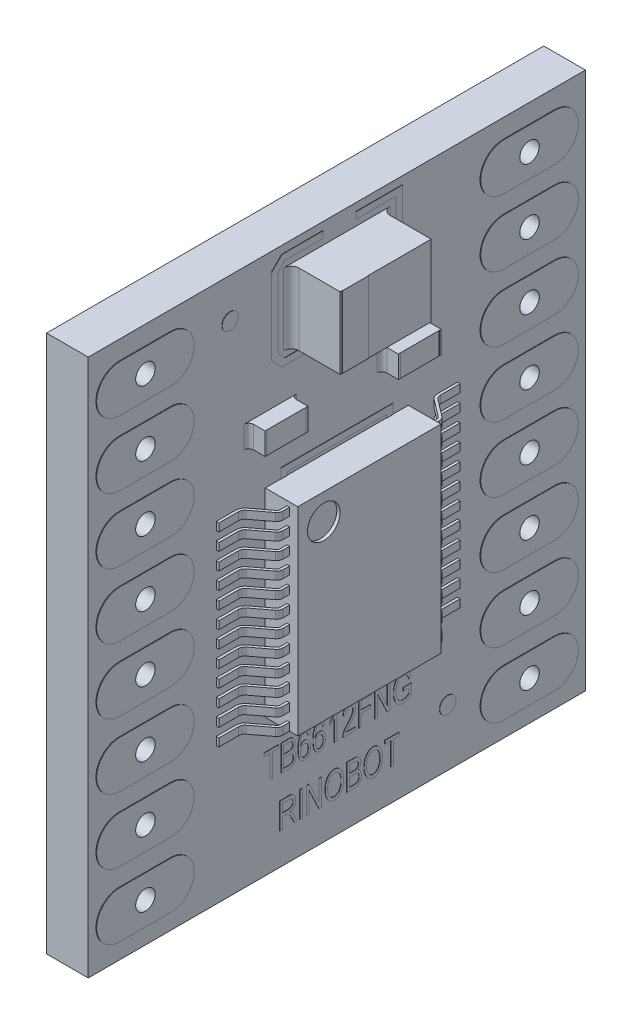
SolidWorks part; units mm, degrees
ref_plane "Front Plane" through (0, 0, 0) normal (0, 0, 1) x (1, 0, 0)
ref_plane "Top Plane" through (0, 0, 0) normal (0, 1, 0) x (1, 0, 0)
ref_plane "Right Plane" through (0, 0, 0) normal (1, 0, 0) x (0, 0, -1)
sketch "Sketch1" plane through (0, 0, 0) normal (1, 0, 0) x (0, 0, -1)
  line L1 (-10.4521, 10.4902) -> (10.4521, 10.4902)
  line L2 (-10.4521, 10.4902) -> (-10.4521, -10.4902)
  line L3 (-10.4521, -10.4902) -> (10.4521, -10.4902)
  line L4 (10.4521, 10.4902) -> (10.4521, -10.4902)
  line L5 (-10.4521, 10.4902) -> (10.4521, -10.4902) construction
  line L6 (-10.4521, -10.4902) -> (10.4521, 10.4902) construction
  point P0 (0, 0)
  dimension "D1" = 20.9804
  dimension "D2" = 20.9042
extrude "base extrudada" add sketch "Sketch1" along normal blind 1.6256
sketch "Sketch2" plane through (1.6256, 0, 0) normal (1, 0, 0) x (0, 0, -1)
  line L0 (-10.4521, -10.4902) -> (10.4521, -10.4902) construction
  line L1 (-2.794, 2.6162) -> (2.794, 2.6162)
  line L2 (-2.794, 2.6162) -> (-2.794, -5.1308)
  line L3 (-2.794, -5.1308) -> (2.794, -5.1308)
  line L4 (2.794, 2.6162) -> (2.794, -5.1308)
  line L5 (-2.794, 2.6162) -> (2.794, -5.1308) construction
  line L6 (-2.794, -5.1308) -> (2.794, 2.6162) construction
  point P0 (0, 0)
  dimension "D1" = 5.588
  dimension "D2" = 7.747
  dimension "D3" = 5.3594
extrude "Ci extrudado" add sketch "Sketch2" along normal blind 1.27
sketch "Sketch7" plane through (2.8956, 0, 0) normal (1, 0, 0) x (0, 0, -1)
  line L0 (-2.794, 2.6162) -> (-2.794, -5.1308) construction
  line L1 (2.794, 2.6162) -> (-2.794, 2.6162) construction
  circle A0 centre (-1.778, 1.6002) radius 0.635
  dimension "D1" = 1.27
  dimension "D2" = 1.016
  dimension "D3" = 1.016
extrude "furo dos Ci's" cut sketch "Sketch7" against normal blind 0.127
sketch "Sketch4" plane through (1.6256, 0, 0) normal (1, 0, 0) x (0, 0, -1)
  line L0 (-7.493, 8.8392) -> (0, 8.8392) construction
  line L1 (0, 8.8392) -> (7.493, 8.8392) construction
  line L2 (0, 0) -> (0, 8.8392) construction
  line L3 (10.4521, 10.4902) -> (-10.4521, 10.4902) construction
  circle A0 centre (-7.493, 8.8392) radius 0.381
  circle A1 centre (7.493, 8.8392) radius 0.381
  dimension "D2" = 0.762
  dimension "D1" = 14.986
  dimension "D3" = 1.27
extrude "furo dos pinos" cut sketch "Sketch4" against normal through all
sketch "Sketch5" plane through (1.6256, 0, 0) normal (1, 0, 0) x (0, 0, -1)
  line L0 (-8.4836, 8.8392) -> (-6.5024, 8.8392) construction
  line L1 (-8.4836, 9.7536) -> (-6.5024, 9.7536)
  line L2 (-8.4836, 7.9248) -> (-6.5024, 7.9248)
  line L3 (6.5024, 8.8392) -> (8.4836, 8.8392) construction
  line L4 (6.5024, 9.7536) -> (8.4836, 9.7536)
  line L5 (6.5024, 7.9248) -> (8.4836, 7.9248)
  arc A0 (-8.4836, 9.7536) -> (-8.4836, 7.9248) centre (-8.4836, 8.8392) ccw
  arc A1 (-6.5024, 7.9248) -> (-6.5024, 9.7536) centre (-6.5024, 8.8392) ccw
  arc A2 (6.5024, 9.7536) -> (6.5024, 7.9248) centre (6.5024, 8.8392) ccw
  arc A3 (8.4836, 7.9248) -> (8.4836, 9.7536) centre (8.4836, 8.8392) ccw
  circle A6 centre (7.493, 8.8392) radius 0.381 construction
  circle A7 centre (-7.493, 8.8392) radius 0.381 construction
  circle A8 centre (7.493, 8.8392) radius 0.381
  circle A9 centre (-7.493, 8.8392) radius 0.381
  point P3 (-7.493, 8.8392)
  point P8 (7.493, 8.8392)
  point P18 (7.493, 8.8392)
  dimension "D2" = 3.81
  dimension "D1" = 1.8288
extrude "base pra solda" add sketch "Sketch5" along normal blind 0.0254
sketch "Sketch6" plane through (0, 0, 0) normal (-1, 0, 0) x (0, 0, 1)
  line L0 (-6.5024, 7.9248) -> (-8.4836, 7.9248) construction
  line L1 (-8.4836, 9.7536) -> (-6.5024, 9.7536) construction
  line L2 (8.4836, 7.9248) -> (6.5024, 7.9248) construction
  line L3 (6.5024, 9.7536) -> (8.4836, 9.7536) construction
  line L4 (-6.5024, 7.9248) -> (-8.4836, 7.9248)
  line L5 (-8.4836, 9.7536) -> (-6.5024, 9.7536)
  line L6 (8.4836, 7.9248) -> (6.5024, 7.9248)
  line L7 (6.5024, 9.7536) -> (8.4836, 9.7536)
  circle A0 centre (-7.493, 8.8392) radius 0.381 construction
  arc A1 (-6.5024, 7.9248) -> (-6.5024, 9.7536) centre (-6.5024, 8.8392) ccw construction
  arc A2 (-8.4836, 9.7536) -> (-8.4836, 7.9248) centre (-8.4836, 8.8392) ccw construction
  circle A3 centre (7.493, 8.8392) radius 0.381 construction
  arc A4 (6.5024, 9.7536) -> (6.5024, 7.9248) centre (6.5024, 8.8392) ccw construction
  arc A5 (8.4836, 7.9248) -> (8.4836, 9.7536) centre (8.4836, 8.8392) ccw construction
  circle A6 centre (-7.493, 8.8392) radius 0.381
  arc A7 (-6.5024, 7.9248) -> (-6.5024, 9.7536) centre (-6.5024, 8.8392) ccw
  arc A8 (-8.4836, 9.7536) -> (-8.4836, 7.9248) centre (-8.4836, 8.8392) ccw
  circle A9 centre (7.493, 8.8392) radius 0.381
  arc A10 (6.5024, 9.7536) -> (6.5024, 7.9248) centre (6.5024, 8.8392) ccw
  arc A11 (8.4836, 7.9248) -> (8.4836, 9.7536) centre (8.4836, 8.8392) ccw
extrude "base pra solda2" add sketch "Sketch6" along normal blind 0.0254
pattern_linear "Padrão Linear Solda" count 8 spacing 2.54 along (0, -1, 0) of "furo dos pinos", "base pra solda", "base pra solda2"
sketch "Sketch11" plane through (1.6256, 0, 0) normal (1, 0, 0) x (0, 0, -1)
  circle A0 centre (-4.1683, 8.9453) radius 0.3175
  circle A1 centre (4.3185, -8.2635) radius 0.3175
  dimension "D1" = 0.635
extrude "furos na placa" add sketch "Sketch11" along normal blind 0.0127
sketch "Sketch9" plane through (1.6256, 0, 0) normal (1, 0, 0) x (0, 0, -1)
  line L0 (-2.6, 4.748) -> (0, 4.748) construction
  line L1 (-3.36, 5.1798) -> (-1.84, 5.1798)
  line L2 (-3.36, 5.1798) -> (-3.36, 4.3162)
  line L3 (-3.36, 4.3162) -> (-1.84, 4.3162)
  line L4 (-1.84, 5.1798) -> (-1.84, 4.3162)
  line L5 (-3.36, 5.1798) -> (-1.84, 4.3162) construction
  line L6 (-3.36, 4.3162) -> (-1.84, 5.1798) construction
  line L7 (1.84, 5.1798) -> (3.36, 5.1798)
  line L8 (1.84, 5.1798) -> (1.84, 4.3162)
  line L9 (1.84, 4.3162) -> (3.36, 4.3162)
  line L10 (3.36, 5.1798) -> (3.36, 4.3162)
  line L11 (1.84, 5.1798) -> (3.36, 4.3162) construction
  line L12 (1.84, 4.3162) -> (3.36, 5.1798) construction
  line L13 (0, 4.748) -> (2.6, 4.748) construction
  line L14 (0, 4.748) -> (0, 0) construction
  line L15 (2.794, 2.6162) -> (-2.794, 2.6162) construction
  point P0 (-2.6, 4.748)
  point P5 (2.6, 4.748)
  dimension "D1" = 0.8636
  dimension "D2" = 1.52
  dimension "D3" = 2.6
  dimension "D4" = 1.7
extrude "resistores" add sketch "Sketch9" along normal blind 0.635
sketch "Sketch10" plane through (1.6256, 0, 0) normal (1, 0, 0) x (0, 0, -1)
  line L1 (-1.84, 5.1798) -> (-1.7638, 5.1798)
  line L2 (-1.84, 5.1798) -> (-1.84, 4.3162)
  line L3 (-1.84, 4.3162) -> (-1.7638, 4.3162)
  line L4 (-1.7638, 5.1798) -> (-1.7638, 4.3162)
  line L5 (-3.36, 5.1798) -> (-3.4362, 5.1798)
  line L6 (-3.36, 5.1798) -> (-3.36, 4.3162)
  line L7 (-3.36, 4.3162) -> (-3.4362, 4.3162)
  line L8 (-3.4362, 5.1798) -> (-3.4362, 4.3162)
  line L9 (1.84, 5.1798) -> (1.7638, 5.1798)
  line L10 (1.84, 5.1798) -> (1.84, 4.3162)
  line L11 (1.84, 4.3162) -> (1.7638, 4.3162)
  line L12 (1.7638, 5.1798) -> (1.7638, 4.3162)
  line L13 (3.36, 5.1798) -> (3.4362, 5.1798)
  line L14 (3.36, 5.1798) -> (3.36, 4.3162)
  line L15 (3.36, 4.3162) -> (3.4362, 4.3162)
  line L16 (3.4362, 5.1798) -> (3.4362, 4.3162)
  line L17 (-3.36, 4.3162) -> (-1.84, 4.3162) construction
  dimension "D1" = 0.0762
extrude "resistores2" add sketch "Sketch10" along normal blind 0.6363
fillet "filete resistores" radius 0.1905 4 edges at (1.6256, 4.748, -3.4362) (1.6256, 4.748, -1.7638) (1.6256, 4.748, 1.7638) (1.6256, 4.748, 3.4362)
sketch "Sketch12" plane through (1.6256, 0, 0) normal (1, 0, 0) x (0, 0, -1)
  line L0 (0, 0) -> (0, 8.2932) construction
  line L1 (-1.778, 6.8962) -> (1.778, 6.8962)
  line L2 (-1.778, 6.8962) -> (-1.778, 9.6902)
  line L3 (-1.778, 9.6902) -> (1.778, 9.6902)
  line L4 (1.778, 6.8962) -> (1.778, 9.6902)
  line L5 (-1.778, 6.8962) -> (1.778, 9.6902) construction
  line L6 (-1.778, 9.6902) -> (1.778, 6.8962) construction
  line L8 (10.4521, 10.4902) -> (-10.4521, 10.4902) construction
  point P0 (0, 8.2932)
  dimension "D1" = 2.794
  dimension "D2" = 3.556
  dimension "D3" = 0.8
extrude "base caxotin" add sketch "Sketch12" along normal blind 1.905
fillet "filete caxotin" radius 0.3048 2 edges at (1.6256, 8.2932, -1.778) (1.6256, 8.2932, 1.778)
sketch "Sketch13" plane through (3.5306, 0, 0) normal (1, 0, 0) x (0, 0, -1)
  line L0 (1.778, 9.6902) -> (-1.778, 9.6902) construction
  line L1 (-1.6958, 9.6902) -> (-0.6798, 9.6902)
  line L2 (-1.6958, 9.6902) -> (-1.6958, 6.8962)
  line L3 (-1.6958, 6.8962) -> (-0.6798, 6.8962)
  line L4 (-0.6798, 9.6902) -> (-0.6798, 6.8962)
  line L5 (-2.0828, 6.8962) -> (2.0828, 6.8962) construction
  dimension "D1" = 1.016
extrude "sensor caxotin" add sketch "Sketch13" along normal blind 0.0127
sketch "Sketch14" plane through (0, -5.1308, 0) normal (0, -1, 0) x (1, 0, 0)
  line L0 (2.5745, -2.794) -> (2.5745, -3.048)
  line L1 (2.8956, -2.794) -> (1.6256, -2.794) construction
  line L2 (2.4739, -3.2504) -> (1.8278, -3.74)
  line L3 (1.7272, -3.9425) -> (1.7272, -4.7045)
  line L4 (2.4729, -2.794) -> (2.4729, -3.048)
  line L5 (2.4126, -3.1695) -> (1.7664, -3.659)
  line L6 (1.6256, -3.9425) -> (1.6256, -4.7045)
  line L7 (2.5745, -2.794) -> (2.4729, -2.794)
  line L8 (1.7272, -4.7045) -> (1.6256, -4.7045)
  line L9 (1.6256, 10.4521) -> (1.6256, -10.4521) construction
  line L10 (2.8956, 0) -> (-1.1531, 0) construction
  line L11 (2.8956, 2.794) -> (2.8956, -2.794) construction
  line L12 (2.5745, 2.794) -> (2.4729, 2.794)
  line L13 (2.5745, 2.794) -> (2.5745, 3.048)
  line L14 (2.4729, 2.794) -> (2.4729, 3.048)
  line L15 (2.4739, 3.2504) -> (1.8278, 3.74)
  line L16 (2.4126, 3.1695) -> (1.7664, 3.659)
  line L17 (1.7272, 3.9425) -> (1.7272, 4.7045)
  line L18 (1.7272, 4.7045) -> (1.6256, 4.7045)
  line L19 (1.6256, 3.9425) -> (1.6256, 4.7045)
  arc A0 (1.8278, -3.74) -> (1.7272, -3.9425) centre (1.9812, -3.9425) ccw
  arc A1 (2.5745, -3.048) -> (2.4739, -3.2504) centre (2.3205, -3.048) cw
  arc A2 (2.4729, -3.048) -> (2.4126, -3.1695) centre (2.3205, -3.048) cw
  arc A3 (1.7664, -3.659) -> (1.6256, -3.9425) centre (1.9812, -3.9425) ccw
  arc A4 (2.4729, 3.048) -> (2.4126, 3.1695) centre (2.3205, 3.048) ccw
  arc A5 (2.5745, 3.048) -> (2.4739, 3.2504) centre (2.3205, 3.048) ccw
  arc A6 (1.7664, 3.659) -> (1.6256, 3.9425) centre (1.9812, 3.9425) cw
  arc A7 (1.8278, 3.74) -> (1.7272, 3.9425) centre (1.9812, 3.9425) cw
  dimension "D1" = 0.254
  dimension "D3" = 232.848
  dimension "D4" = 0.254
  dimension "D5" = 0.762
  dimension "D2" = 0.1016
extrude "perna Ci" add sketch "Sketch14" against normal blind 0.3048
pattern_linear "Padrão Linear pernas" count 12 spacing 0.6604 along (0, 1, 0) of "perna Ci"
sketch "Sketch8" plane through (1.6256, 0, 0) normal (1, 0, 0) x (0, 0, -1)
  line L0 (-2.1843, 2.9972) -> (2.1843, 2.9972)
  line L1 (-1.9303, 2.7432) -> (1.9303, 2.7432)
  line L2 (-1.9303, 2.7432) -> (-1.9303, -5.2578)
  line L3 (-1.9303, -5.2578) -> (1.9303, -5.2578)
  line L4 (1.9303, 2.7432) -> (1.9303, -5.2578)
  line L5 (-1.9303, 2.7432) -> (1.9303, -5.2578) construction
  line L6 (-1.9303, -5.2578) -> (1.9303, 2.7432) construction
  line L7 (2.1843, 2.9972) -> (2.1843, -5.5118)
  line L8 (-2.1843, -5.5118) -> (2.1843, -5.5118)
  line L9 (-2.1843, 2.9972) -> (-2.1843, -5.5118)
  line L10 (2.794, 2.6162) -> (-2.794, 2.6162) construction
  line L11 (-0.5427, 10.1902) -> (-0.5427, 9.9362)
  line L12 (-2.794, -5.1308) -> (2.794, -5.1308) construction
  line L13 (2.5533, 10.1902) -> (2.5533, 6.3871)
  line L14 (-2.0453, 9.9362) -> (-0.5427, 9.9362)
  line L15 (-2.2993, 9.6822) -> (-2.2993, 6.8951)
  line L16 (-2.0453, 6.6411) -> (-0.5427, 6.6411)
  line L17 (2.2993, 9.9362) -> (2.2993, 6.6411)
  line L18 (-2.2993, 9.9362) -> (-2.2993, 6.6411) construction
  line L19 (-2.2993, 9.6822) -> (-2.0453, 9.9362)
  line L20 (-2.1505, 6.3871) -> (-0.5427, 6.3871)
  line L21 (-2.5533, 9.7874) -> (-2.1505, 10.1902)
  line L22 (-2.1505, 10.1902) -> (-0.5427, 10.1902)
  line L23 (0.7387, 10.1902) -> (0.7387, 9.9362)
  line L24 (0.7387, 10.1902) -> (2.5533, 10.1902)
  line L25 (-2.5533, 10.1902) -> (2.5533, 10.1902) construction
  line L26 (0.7387, 9.9362) -> (2.2993, 9.9362)
  line L27 (-2.2993, 9.9362) -> (2.2993, 9.9362) construction
  line L28 (-2.2993, 6.8951) -> (-2.0453, 6.6411)
  line L29 (-2.5533, 6.7898) -> (-2.1505, 6.3871)
  line L30 (0.7387, 6.6411) -> (2.2993, 6.6411)
  line L31 (-2.2993, 6.6411) -> (2.2993, 6.6411) construction
  line L32 (0.7387, 6.3871) -> (2.5533, 6.3871)
  line L33 (-2.5533, 6.3871) -> (2.5533, 6.3871) construction
  line L34 (0.7387, 6.6411) -> (0.7387, 6.3871)
  line L35 (-0.5427, 6.6411) -> (-0.5427, 6.3871)
  line L36 (-2.5533, 10.1902) -> (-2.5533, 6.3871) construction
  line L37 (-2.5533, 9.7874) -> (-2.5533, 6.7898)
  line L38 (-2.4789, 9.8618) -> (-2.2249, 10.1158) construction
  line L39 (-2.4789, 6.7154) -> (-2.2249, 6.4614) construction
  line L40 (-2.5533, 9.6822) -> (-2.5533, 6.8951) construction
  line L41 (10.4521, 10.4902) -> (-10.4521, 10.4902) construction
  text T0 "     TB6612FNG\r\n       RINOBOT" font "Arial Narrow" height 1.016
  point P1 (0, -1.2573)
  point P14 (0, 6.4262)
  dimension "D2" = 0.127
  dimension "D3" = 0.127
  dimension "D5" = 0.254
  dimension "D8" = 0.3
  dimension "D9" = 1.5026
  dimension "D10" = 2.9976
  dimension "D11" = 3.8031
  dimension "D12" = 1.5026
  dimension "D13" = 1.8146
  dimension "D14" = 2.7871
  dimension "D15" = 0.5696
  dimension "D1" = 0.254
  dimension "D4" = 0.254
  dimension "D6" = 0.254
  dimension "D7" = 0.254
extrude "trilha da placa" add sketch "Sketch8" along normal blind 0.0127
sketch "Sketch15" plane through (0, 0, 0) normal (-1, 0, 0) x (0, 0, 1)
  line L0 (5.2079, 12.1114) -> (5.2079, -12.5412) construction
  text T0 "PWMA" font "Century Gothic" height 1.016
  text T1 "AIN2" font "Century Gothic" height 1.016
  text T2 "AIN1" font "Century Gothic" height 1.016
  text T3 "STBY" font "Century Gothic" height 1.016
  text T4 "BIN1" font "Century Gothic" height 1.016
  text T5 "BIN2" font "Century Gothic" height 1.016
  text T6 "PWMB" font "Century Gothic" height 1.016
  text T7 "GND" font "Century Gothic" height 1.016
  text T8 "VM" font "Century Gothic" height 1.016
  text T9 "VCC" font "Century Gothic" height 1.016
  text T10 "GND" font "Century Gothic" height 1.016
  text T11 "A01" font "Century Gothic" height 1.016
  text T12 "A02" font "Century Gothic" height 1.016
  text T13 "B02" font "Century Gothic" height 1.016
  text T14 "B01" font "Century Gothic" height 1.016
  text T15 "GND" font "Century Gothic" height 1.016
extrude "nome dos pinos" add sketch "Sketch15" along normal blind 0.0254
sketch "Esboço1" plane through (1.6256, 0, 0) normal (1, 0, 0) x (0, 0, -1)
  line L2 (-9.7, 10.4902) -> (-9.7, -10.4902)
  line L4 (9.7, 10.4902) -> (9.7, -10.4902)
  line L5 (-9.4624, 10.4902) -> (9.4624, -10.4902) construction
  line L6 (-9.4624, -10.4902) -> (9.4624, 10.4902) construction
  line L11 (10.4521, 10.4902) -> (-10.4521, 10.4902) construction
  line L12 (-10.4521, -10.4902) -> (10.4521, -10.4902) construction
  line L13 (10.4521, -10.4902) -> (10.4521, 10.4902) construction
  line L14 (-10.4521, 10.4902) -> (-10.4521, -10.4902) construction
  line L15 (10.4521, 10.4902) -> (-10.4521, 10.4902)
  line L16 (-10.4521, -10.4902) -> (10.4521, -10.4902)
  line L17 (10.4521, -10.4902) -> (10.4521, 10.4902)
  line L18 (-10.4521, 10.4902) -> (-10.4521, -10.4902)
  point P0 (0, 0)
extrude "Corte-extrusão1" cut sketch "Esboço1" against normal through all contours L15 L18 L16 L2 | L16 L17 L15 L4
